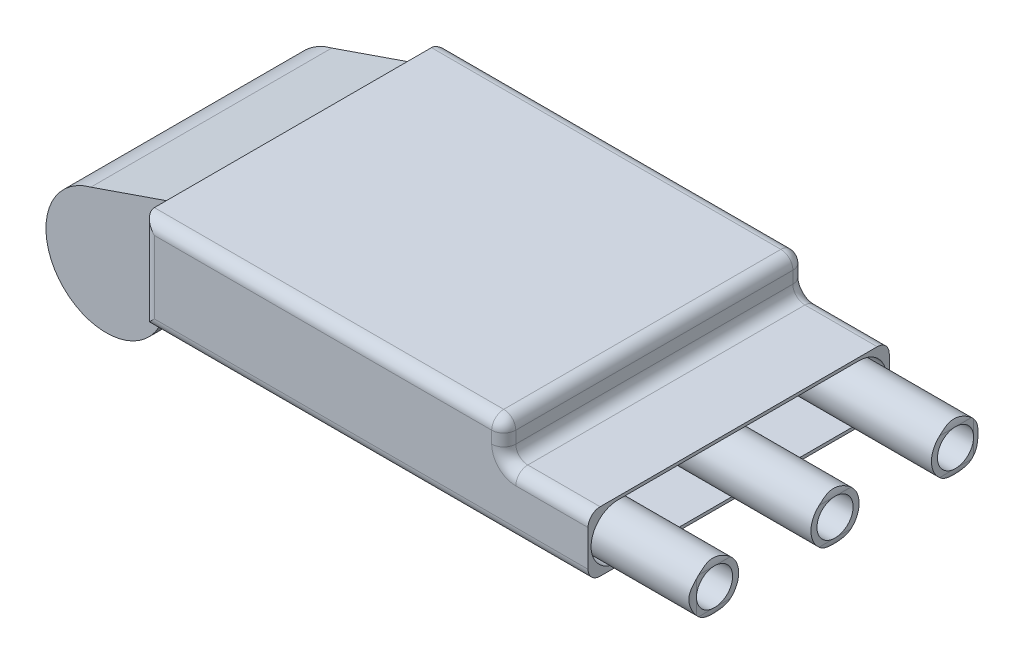
SolidWorks part; units mm, degrees
ref_plane "Ön Düzlem" through (0, 0, 0) normal (0, 0, 1) x (1, 0, 0)
ref_plane "Üst Düzlem" through (0, 0, 0) normal (0, 1, 0) x (1, 0, 0)
ref_plane "Sağ Düzlem" through (0, 0, 0) normal (1, 0, 0) x (0, 0, -1)
sketch "Çizim1" plane through (0, 0, 0) normal (0, 1, 0) x (1, 0, 0)
  line L1 (-7.5, -12.5) -> (7.5, -12.5)
  line L2 (-7.5, -12.5) -> (-7.5, 12.5)
  line L3 (-7.5, 12.5) -> (7.5, 12.5)
  line L4 (7.5, -12.5) -> (7.5, 12.5)
  line L5 (-7.5, -12.5) -> (7.5, 12.5) construction
  line L6 (-7.5, 12.5) -> (7.5, -12.5) construction
  point P0 (0, 0)
  dimension "D1" = 15
  dimension "D2" = 25
extrude "Yükseklik-Ekstrüzyon1" add sketch "Çizim1" along normal blind 5
sketch "Çizim2" plane through (-7.5, 0, 0) normal (-1, 0, 0) x (0, 0, 1)
  line L1 (-12.5, 0) -> (12.5, 0)
  line L2 (-12.5, 0) -> (-12.5, 8)
  line L3 (-12.5, 8) -> (12.5, 8)
  line L4 (12.5, 0) -> (12.5, 8)
  dimension "D1" = 8
extrude "Yükseklik-Ekstrüzyon2" add sketch "Çizim2" along normal blind 30
ref_plane "Düzlem1" through (0, 0, 12.5) normal (0, 0, 1) x (1, 0, 0)
sketch "Çizim3" plane through (0, 0, 12.5) normal (0, 0, 1) x (1, 0, 0)
  line L0 (-37.5, 6) -> (-57.6129, 6) construction
  line L1 (-37.5, 0) -> (-37.5, 6)
  line L2 (-37.5, 0) -> (-37.5, 8) construction
  circle A0 centre (-42.5, 1) radius 5
  dimension "D1" = 10
  dimension "D2" = 6
extrude "Yükseklik-Ekstrüzyon3" add sketch "Çizim3" against normal blind 20 from offset 2 separate body contours A0 region at (-42.5, 1, 12.5) offset against normal yes
sketch "Çizim6" plane through (0, 0, 10.5) normal (0, 0, 1) x (1, 0, 0)
  line L0 (-37.5, 8) -> (-43.7745, 5.8348)
  line L1 (-37.5, 8) -> (-37.5, 1)
  circle A0 centre (-42.5, 1) radius 5 construction
  circle A1 centre (-42.5, 1) radius 5
  circle M1 centre (-42.5, 1) radius 5
extrude "Yükseklik-Ekstrüzyon4" add sketch "Çizim6" against normal blind 20 contours L1 L0 M1 region at (-39.0515, 5.8097, 10.5)
fillet "Radyus2" radius 1 16 edges at (-7.5, 6.5, 12.5) (7.5, 2.5, -12.5) (-7.5, 6.5, -12.5) (-22.5, 8, -12.5) (-37.5, 4, -12.5) (-15, 0, -12.5) (0, 5, 12.5) (-7.5, 5, 0) (0, 5, -12.5) (7.5, 5, 0) (-37.5, 4, 12.5) (7.5, 0, 0) (-15, 0, 12.5) (-22.5, 8, 12.5) (-7.5, 8, 0) (7.5, 2.5, 12.5)
sketch "Çizim8" plane through (7.5, 0, 0) normal (1, 0, 0) x (0, 0, -1)
  line L0 (-11.5, 2.5) -> (11.5, 2.5) construction
  line L1 (-11.5, 4) -> (-11.5, 1) construction
  line L2 (11.5, 1) -> (11.5, 4) construction
  line L3 (-10, 2.5) -> (10, 2.5) construction
  line L4 (12, 2.5) -> (12.5, 2.5) construction
  line L5 (-10, 4.75) -> (10, 4.75)
  line L6 (-10, 0.25) -> (10, 0.25)
  line L7 (12.5, 4) -> (12.5, 1) construction
  line L8 (-10, 4.5) -> (-10, 5) construction
  line L9 (11.5, 5) -> (-11.5, 5) construction
  line L13 (10, 0.5) -> (10, 0.3) construction
  circle A0 centre (0, 2.5) radius 2
  circle A1 centre (-10, 2.5) radius 2
  circle A2 centre (10, 2.5) radius 2
  circle A3 centre (-10, 2.5) radius 1.5
  circle A4 centre (0, 2.5) radius 1.5
  circle A5 centre (10, 2.5) radius 1.5
  arc A6 (-10, 4.75) -> (-10, 0.25) centre (-10, 2.5) ccw
  arc A7 (10, 0.25) -> (10, 4.75) centre (10, 2.5) ccw
  point P17 (0, 2.5)
  point P27 (12.25, 2.5)
  point P33 (-10, 4.75)
  line M7 (-11.5, 1) -> (11.5, 1)
  line M8 (11.5, 1) -> (11.5, 4)
  line M9 (11.5, 4) -> (-11.5, 4)
  line M10 (-11.5, 4) -> (-11.5, 1)
  dimension "D1" = 4
  dimension "D4" = 3
  dimension "D2" = 10
  dimension "D3" = 10
  dimension "D5" = 0.25
extrude "Kes-Ekstrüzyon1" cut sketch "Çizim8" against normal blind 20 contours A5 | L6 A7 L5 A6 A2 A0 A1 M9 M8 M7 M10 | A3 | A4 | A1 A0 M7 M9 | A2 A0 M9 M7 | A2 M8 M9 | A2 M7 M8 | A1 M9 M10 | A1 M10 M7 region at (7.5, 4.5009, 0) region at (7.5, 2.5, -5) region at (7.5, 2.5, 5) region at (7.5, 2.5, 0) region at (7.5, 3.9422, -11.4422) region at (7.5, 2.5, -10) region at (7.5, 1.0578, -11.4422) region at (7.5, 3.9422, 11.4422) region at (7.5, 2.5, 10) region at (7.5, 1.0578, 11.4422)
sketch "Çizim9" plane through (7.5, 0, 0) normal (1, 0, 0) x (0, 0, -1)
  line L0 (-10, 2.5) -> (10, 2.5) construction
  line L1 (-10, 4.6223) -> (10, 4.6223)
  line L2 (-10, 0.3777) -> (10, 0.3777)
  line L3 (-10, 2.5) -> (10, 2.5) construction
  line L4 (-10, 6.1803) -> (10, 6.1803)
  line L5 (-10, -1.1803) -> (10, -1.1803)
  arc A0 (-10, 4.6223) -> (-10, 0.3777) centre (-10, 2.5) ccw
  arc A1 (10, 0.3777) -> (10, 4.6223) centre (10, 2.5) ccw
  arc A2 (-10, 6.1803) -> (-10, -1.1803) centre (-10, 2.5) ccw
  arc A3 (10, -1.1803) -> (10, 6.1803) centre (10, 2.5) ccw
  point P2 (0, 2.5)
  point P11 (0, 2.5)
extrude "Kes-Ekstrüzyon2" cut sketch "Çizim9" against normal blind 8
